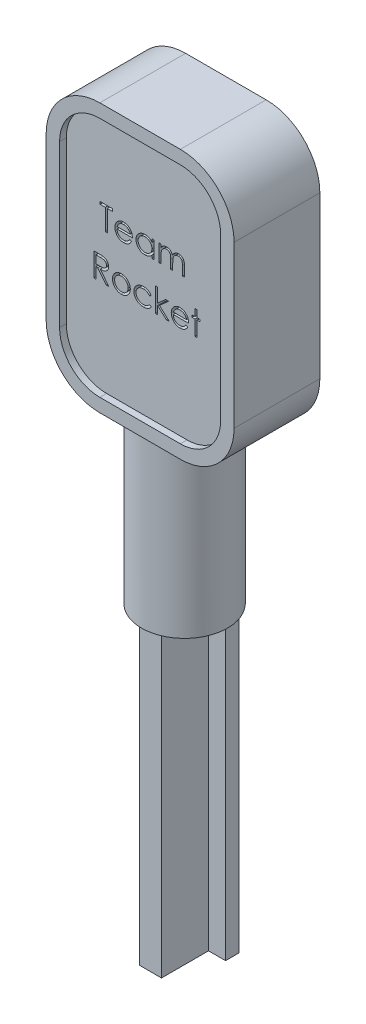
SolidWorks part; units mm, degrees
ref_plane "Front Plane" through (0, 0, 0) normal (0, 0, 1) x (1, 0, 0)
ref_plane "Top Plane" through (0, 0, 0) normal (0, 1, 0) x (1, 0, 0)
ref_plane "Right Plane" through (0, 0, 0) normal (1, 0, 0) x (0, 0, -1)
sketch "Sketch7" plane through (0, 0, 0) normal (0, 1, 0) x (1, 0, 0)
  line L0 (-1.9605, 10.8472) -> (-1.9605, -11.7967) construction
  line L1 (-14.1649, 0.3217) -> (15.1085, 0.3217) construction
  line L2 (-6.1286, 4.5881) -> (2.2077, 4.5881)
  line L3 (-6.1286, 4.5881) -> (-6.1286, 2.6174)
  line L4 (-1.9568, 6.9234) -> (-1.9568, -6.9234) construction
  line L5 (-11.0689, 0.3417) -> (11.0689, 0.3417) construction
  line L6 (-6.1286, 2.6174) -> (2.2077, 2.6174)
  line L7 (2.2077, 4.5881) -> (2.2077, 2.6174)
  line L8 (-6.1286, 4.5881) -> (2.2077, 2.6174) construction
  line L9 (-6.1286, 2.6174) -> (2.2077, 4.5881) construction
  line L10 (-3.5885, -4.3868) -> (-0.3324, -4.3868)
  line L11 (-3.5885, -4.3868) -> (-3.5885, 2.6174)
  line L12 (-3.5885, 2.6174) -> (-0.3324, 2.6174)
  line L13 (-0.3324, -4.3868) -> (-0.3324, 2.6174)
  line L14 (-3.5885, -4.3868) -> (-0.3324, 2.6174) construction
  line L15 (-3.5885, 2.6174) -> (-0.3324, -4.3868) construction
  circle A1 centre (-1.9568, 0.3417) radius 6.4522
  point P8 (-1.9605, 3.6028)
  point P13 (-1.9605, -0.8847)
extrude "Boss-Extrude4" add sketch "Sketch7" along normal blind 45 contours L10 L13 L6 L11 | L7 L2 L3 L6 region at (-1.9605, 0, -3.6028) region at (-1.9605, 0, 0.8847)
sketch "Sketch13" plane through (0, 45, 0) normal (0, 1, 0) x (1, 0, 0)
  line L0 (-1.9605, -4.3868) -> (-1.9605, 15.5303) construction
  line L1 (-3.5885, -4.3868) -> (-0.3324, -4.3868) construction
  circle A0 centre (-1.9605, 0.6726) radius 6.4
extrude "Boss-Extrude7" add sketch "Sketch13" along normal blind 25
sketch "Sketch9" plane through (0, 45, 0) normal (0, -1, 0) x (-1, 0, 0)
  line L0 (-2.55, 0.6726) -> (17.652, 0.6726) construction
  circle A0 centre (1.9605, 0.6726) radius 6.3911 construction
  circle A1 centre (1.9605, 0.6726) radius 6.3911
  circle A2 centre (1.6963, 7.0571) radius 0.0101
  circle A3 centre (1.9605, 0.6726) radius 6.4 construction
sketch "Sketch10" plane through (0, 70, 0) normal (0, 1, 0) x (1, 0, 0)
  line L0 (-15.8587, -6.0494) -> (-15.8587, 6.7327)
  line L1 (-15.8587, -6.0494) -> (12.1413, -6.0494)
  line L2 (-15.8587, 6.7327) -> (12.1413, 6.7327)
  line L3 (12.1413, -6.0494) -> (12.1413, 6.7327)
  line L4 (-15.8587, -6.0494) -> (12.1413, 6.7327) construction
  line L5 (-15.8587, 6.7327) -> (12.1413, -6.0494) construction
  circle A0 centre (3.2555, 4.2368) radius 0.0375
  point P1 (-1.8587, 0.3417)
extrude "Boss-Extrude6" add sketch "Sketch10" along normal blind 40
fillet "Fillet3" radius 8 1 edges at (12.1413, 70, -0.3417) type face fillet first side face at (-1.8926, 70, -0.3954) second side face at (12.1413, 90, -0.3417)
fillet "Fillet4" radius 8 1 edges at (-15.8587, 70, -0.3417) type face fillet first side face at (-6.7906, 70, 1.3057) second side face at (-15.8587, 90, -0.3417)
fillet "Fillet5" radius 8 1 edges at (12.1413, 110, -0.3417) type face fillet first side face at (12.1413, 94, -0.3417) second side face at (-1.8587, 110, -0.3417)
fillet "Fillet6" radius 8 1 edges at (-15.8587, 110, -0.3417) type face fillet first side face at (-15.8587, 94, -0.3417) second side face at (-5.8587, 110, -0.3417)
sketch "Sketch11" plane through (0, 0, -6.7327) normal (0, 0, -1) x (-1, 0, 0)
  line L7 (4.0184, 72) -> (7.8587, 72)
  line L8 (4.0184, 72) -> (7.8587, 72)
  line L9 (-0.0975, 72) -> (4.0184, 72)
  line L10 (-0.0975, 72) -> (4.0184, 72)
  line L15 (13.8587, 78) -> (13.8587, 102)
  line L16 (7.8587, 108) -> (-4.1413, 108)
  line L17 (-10.1413, 102) -> (-10.1413, 78)
  line L18 (-4.1413, 72) -> (-0.0975, 72)
  line L20 (13.8587, 78) -> (13.8587, 102)
  line L21 (7.8587, 108) -> (-4.1413, 108)
  line L22 (-10.1413, 102) -> (-10.1413, 78)
  line L23 (-4.1413, 72) -> (-0.0975, 72)
  arc A12 (13.8587, 102) -> (7.8587, 108) centre (7.8587, 102) ccw
  arc A13 (-4.1413, 108) -> (-10.1413, 102) centre (-4.1413, 102) ccw
  arc A14 (-10.1413, 78) -> (-4.1413, 72) centre (-4.1413, 78) ccw
  arc A15 (7.8587, 72) -> (13.8587, 78) centre (7.8587, 78) ccw
  arc A16 (13.8587, 102) -> (7.8587, 108) centre (7.8587, 102) ccw
  arc A17 (-4.1413, 108) -> (-10.1413, 102) centre (-4.1413, 102) ccw
  arc A18 (-10.1413, 78) -> (-4.1413, 72) centre (-4.1413, 78) ccw
  arc A19 (7.8587, 72) -> (13.8587, 78) centre (7.8587, 78) ccw
  dimension "D1" = 2
extrude "Cut-Extrude1" cut sketch "Sketch11" against normal blind 1 contours L20 A16 L21 A17 L22 A18 L23 L10 L8 A19
sketch "Sketch12" plane through (0, 0, 6.0494) normal (0, 0, 1) x (1, 0, 0)
  line L10 (4.1413, 108) -> (-7.8587, 108)
  line L11 (-13.8587, 102) -> (-13.8587, 78)
  line L12 (-7.8587, 72) -> (4.1413, 72)
  line L14 (10.1413, 78) -> (10.1413, 102)
  line L15 (4.1413, 108) -> (-7.8587, 108)
  line L16 (-13.8587, 102) -> (-13.8587, 78)
  line L17 (-7.8587, 72) -> (4.1413, 72)
  line L19 (10.1413, 78) -> (10.1413, 102)
  arc A8 (-7.8587, 108) -> (-13.8587, 102) centre (-7.8587, 102) ccw
  arc A9 (-13.8587, 78) -> (-7.8587, 72) centre (-7.8587, 78) ccw
  arc A10 (4.1413, 72) -> (10.1413, 78) centre (4.1413, 78) ccw
  arc A11 (10.1413, 102) -> (4.1413, 108) centre (4.1413, 102) ccw
  arc A12 (-7.8587, 108) -> (-13.8587, 102) centre (-7.8587, 102) ccw
  arc A13 (-13.8587, 78) -> (-7.8587, 72) centre (-7.8587, 78) ccw
  arc A14 (4.1413, 72) -> (10.1413, 78) centre (4.1413, 78) ccw
  arc A15 (10.1413, 102) -> (4.1413, 108) centre (4.1413, 102) ccw
  dimension "D1" = 2
extrude "Cut-Extrude2" cut sketch "Sketch12" against normal blind 1
sketch "Sketch14" plane through (0, 0, 5.0494) normal (0, 0, 1) x (1, 0, 0)
  text T0 " Team\r\nRocket"
extrude "Cut-Extrude3" cut sketch "Sketch14" against normal blind 2
